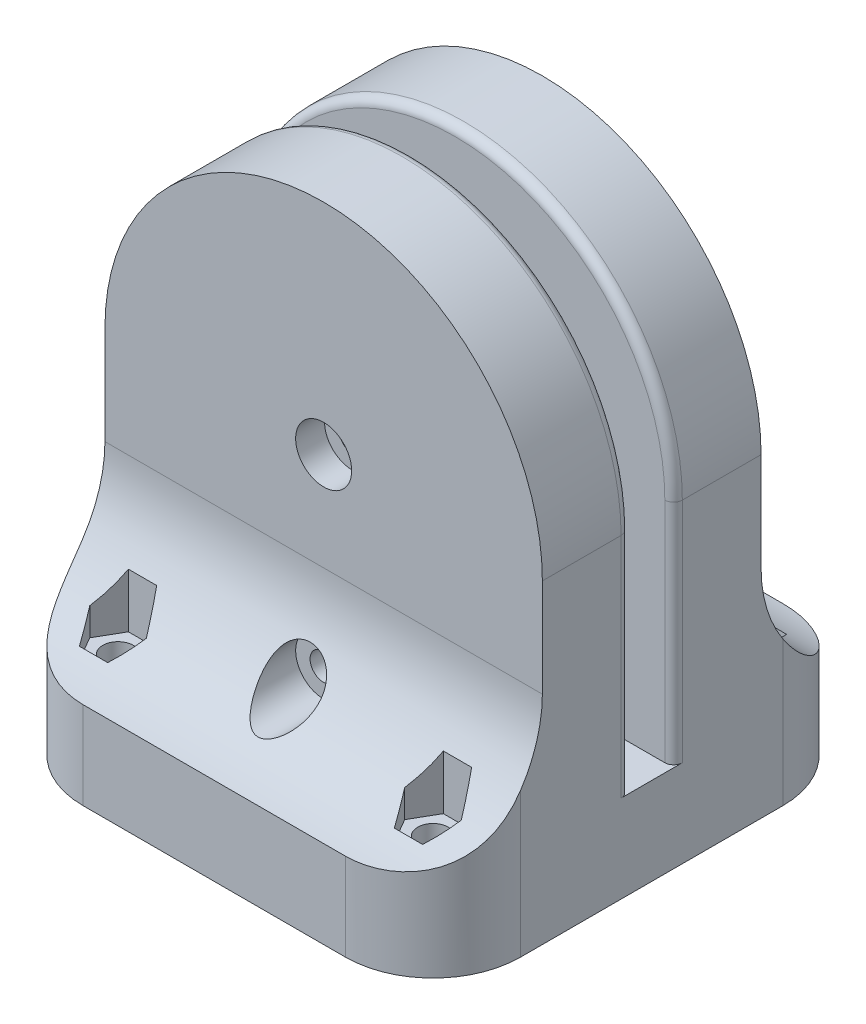
SolidWorks part; units mm, degrees
ref_plane "正面" through (0, 0, 0) normal (0, 0, 1) x (1, 0, 0)
ref_plane "平面" through (0, 0, 0) normal (0, 1, 0) x (1, 0, 0)
ref_plane "右側面" through (0, 0, 0) normal (1, 0, 0) x (0, 0, -1)
sketch "ｽｹｯﾁ1" plane through (0, 0, 0) normal (0, 1, 0) x (1, 0, 0)
  line L1 (25, 25) -> (-25, 25)
  line L2 (25, 25) -> (25, -25)
  line L3 (25, -25) -> (-25, -25)
  line L4 (-25, 25) -> (-25, -25)
  line L5 (25, 25) -> (-25, -25) construction
  line L6 (25, -25) -> (-25, 25) construction
  point P0 (0, 0)
  dimension "D1" = 50
  dimension "D2" = 50
extrude "ﾎﾞｽ - 押し出し1" add sketch "ｽｹｯﾁ1" along normal blind 10
sketch "ｽｹｯﾁ2" plane through (0, 0, 0) normal (0, 0, 1) x (1, 0, 0)
  line L0 (25, 10) -> (-25, 10)
  line L1 (-25, 10) -> (25, 10)
  line L4 (-25, 36) -> (-25, 10)
  line L5 (-25, 10) -> (25, 10)
  line L6 (-12, 10) -> (6.5, 10)
  line L7 (-25, 10) -> (25, 10)
  line L8 (25, 36) -> (25, 10)
  arc A1 (25, 36) -> (-25, 36) centre (0, 36) ccw
  circle A2 centre (0, 36) radius 1.55
  dimension "D1" = 26
  dimension "D3" = 0
  dimension "D2" = 25
  dimension "3.1" = 3.1
  dimension "D4" = 26
  dimension "D5" = 26
sketch "ｽｹｯﾁ6" plane through (0, 0, 0) normal (0, 1, 0) x (1, 0, 0)
  line L0 (0, -25) -> (0, 25) construction
  line L1 (-25, -25) -> (25, -25) construction
  line L2 (25, 25) -> (-25, 25) construction
  line L3 (-25, 0) -> (25, 0) construction
  line L4 (-25, 25) -> (-25, -25) construction
  line L5 (25, -25) -> (25, 25) construction
  circle A0 centre (-18, -18) radius 1.75
  circle A1 centre (18, -18) radius 1.75
  circle A2 centre (18, 18) radius 1.75
  circle A3 centre (-18, 18) radius 1.75
  dimension "D1" = 3.5
  dimension "D2" = 18
  dimension "D3" = 18
extrude "ｶｯﾄ - 押し出し3" cut sketch "ｽｹｯﾁ6" against normal blind 5 and the other way through all
fillet "ﾌｨﾚｯﾄ1" radius 10 4 edges at (-25, 5, 25) (-25, 5, -25) (25, 5, -25) (25, 5, 25)
extrude "ﾎﾞｽ - 押し出し5" add sketch "ｽｹｯﾁ2" along normal blind 10 from offset 2.5 contours L8 A1 L4 L0 L5 A2 region at (0, 33.1492, 0)
extrude "ﾎﾞｽ - 押し出し6" add sketch "ｽｹｯﾁ2<12>" against normal blind 10 from offset 2.5 contours L8 A1 L4 L0 L5 A2 region at (0, 33.1492, 0) offset against normal yes
sketch "ｽｹｯﾁ2<12>" plane through (0, 0, 0) normal (0, 0, 1) x (1, 0, 0) same geometry as "ｽｹｯﾁ2"
sketch "ｽｹｯﾁ13" plane through (0, 0, 0) normal (0, 0, 1) x (1, 0, 0)
  circle A0 centre (0, 36) radius 21
  circle A1 centre (0, 15) radius 1.55
  point P10 (0, 36)
  dimension "D1" = 42
  dimension "3.1" = 3.1
extrude "ｶｯﾄ - 押し出し4" cut sketch "ｽｹｯﾁ13" against normal through all both and the other way through all contours A1
sketch "ｽｹｯﾁ14" plane through (0, 10, 0) normal (0, 1, 0) x (1, 0, 0)
  line L0 (0, 25) -> (0, -25) construction
  line L1 (15, 25) -> (-15, 25) construction
  line L2 (-15, -25) -> (15, -25) construction
  line L3 (-25, 0) -> (25, 0) construction
  line L4 (-25, 2.5) -> (-25, -2.5) construction
  line L5 (25, -2.5) -> (25, 2.5) construction
  line L6 (-19.6166, 15.2) -> (-21.2332, 18)
  line L7 (21.2332, 18) -> (19.6166, 20.8)
  line L8 (19.6166, 20.8) -> (16.3834, 20.8)
  line L9 (16.3834, 20.8) -> (14.7668, 18)
  line L10 (14.7668, 18) -> (16.3834, 15.2)
  line L11 (16.3834, 15.2) -> (19.6166, 15.2)
  line L12 (19.6166, 15.2) -> (21.2332, 18)
  line L13 (-16.3834, 15.2) -> (-19.6166, 15.2)
  line L14 (-14.7668, 18) -> (-16.3834, 15.2)
  line L15 (-16.3834, 20.8) -> (-14.7668, 18)
  line L16 (-19.6166, 20.8) -> (-16.3834, 20.8)
  line L17 (-21.2332, 18) -> (-19.6166, 20.8)
  line L18 (16.3834, -15.2) -> (19.6166, -15.2)
  line L19 (14.7668, -18) -> (16.3834, -15.2)
  line L20 (16.3834, -20.8) -> (14.7668, -18)
  line L21 (19.6166, -20.8) -> (16.3834, -20.8)
  line L22 (21.2332, -18) -> (19.6166, -20.8)
  line L23 (-21.2332, -18) -> (-19.6166, -20.8)
  line L24 (-19.6166, -20.8) -> (-16.3834, -20.8)
  line L25 (-16.3834, -20.8) -> (-14.7668, -18)
  line L26 (-14.7668, -18) -> (-16.3834, -15.2)
  line L27 (-16.3834, -15.2) -> (-19.6166, -15.2)
  line L28 (19.6166, -15.2) -> (21.2332, -18)
  line L29 (-19.6166, -15.2) -> (-21.2332, -18)
  circle A0 centre (18, 18) radius 2.8 construction
  circle A1 centre (-18, 18) radius 2.8 construction
  circle A2 centre (18, -18) radius 2.8 construction
  circle A3 centre (-18, -18) radius 2.8 construction
  dimension "5.6" = 5.6
fillet "ﾌｨﾚｯﾄ3" radius 15 2 edges at (0, 10, -12.5)
sketch "ｽｹｯﾁ15" plane through (0, 0, 0) normal (0, 0, 1) x (1, 0, 0)
  circle A0 centre (0, 15) radius 3.2
  dimension "D1" = 6.4
extrude "ｶｯﾄ - 押し出し7" cut sketch "ｽｹｯﾁ15" along normal through all from offset 12.5
extrude "ｶｯﾄ - 押し出し8" cut sketch "ｽｹｯﾁ15<2>" against normal through all from offset 12.5 offset against normal yes
sketch "ｽｹｯﾁ15<2>" plane through (0, 0, 0) normal (0, 0, 1) x (1, 0, 0) same geometry as "ｽｹｯﾁ15"
sketch "ｽｹｯﾁ16" plane through (0, 0, 0) normal (0, 0, 1) x (1, 0, 0)
  circle A0 centre (0, 36) radius 3.2
  dimension "D1" = 6.4
extrude "ｶｯﾄ - 押し出し9" cut sketch "ｽｹｯﾁ16" against normal blind 3.3 from offset 12.5
extrude "ｶｯﾄ - 押し出し10" cut sketch "ｽｹｯﾁ16<2>" along normal blind 3.3 from offset 12.5 offset against normal yes
sketch "ｽｹｯﾁ16<2>" plane through (0, 0, 0) normal (0, 0, 1) x (1, 0, 0) same geometry as "ｽｹｯﾁ16"
fillet "ﾌｨﾚｯﾄ5" radius 1 6 edges at (25, 23, -2.5) (-25, 23, -2.5) (0, 61, -2.5) (0, 61, 2.5)
extrude "ｶｯﾄ - 押し出し11" cut sketch "ｽｹｯﾁ14" along normal through all
